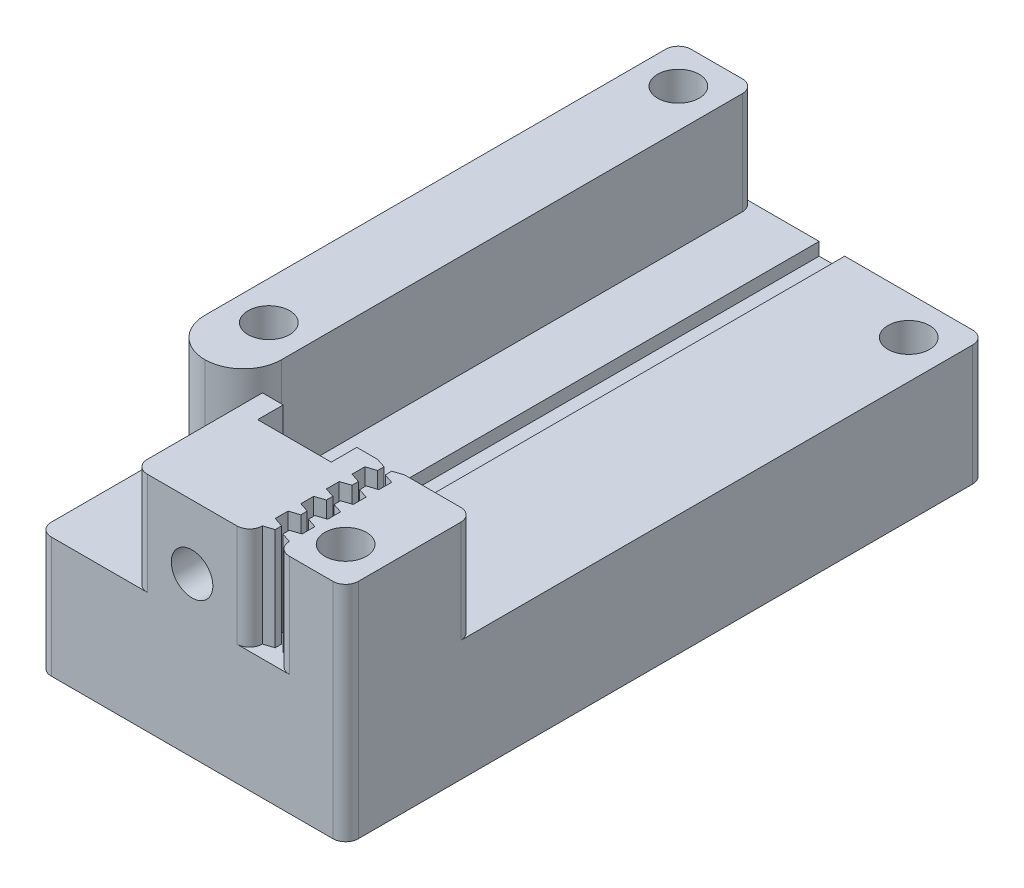
SolidWorks part; units mm, degrees
ref_plane "Front Plane" through (0, 0, 0) normal (0, 0, 1) x (1, 0, 0)
ref_plane "Top Plane" through (0, 0, 0) normal (0, 1, 0) x (1, 0, 0)
ref_plane "Right Plane" through (0, 0, 0) normal (1, 0, 0) x (0, 0, -1)
sketch "Sketch1" plane through (0, 0, 0) normal (0, 1, 0) x (1, 0, 0)
  line L0 (-12, 25) -> (12, -25) construction
  line L1 (-12, 25) -> (12, 25)
  line L2 (-12, 25) -> (-12, -25)
  line L3 (-12, -25) -> (12, -25)
  line L4 (12, 25) -> (12, -25)
  dimension "D1" = 24
  dimension "D2" = 50
extrude "Boss-Extrude1" add sketch "Sketch1" along normal blind 9.42
sketch "Sketch2" plane through (0, 9.42, 0) normal (0, 1, 0) x (1, 0, 0)
  line L0 (-12, -25) -> (12, -25) construction
  line L1 (-12, 25) -> (-6, 25)
  line L2 (-12, 25) -> (-12, -15)
  line L3 (-12, -15) -> (-6, -15)
  line L4 (-6, 25) -> (-6, -15)
  line L6 (-4.5, -25) -> (4.5, -25)
  line L7 (-4.5, -25) -> (-4.5, -15)
  line L8 (-4.5, -15) -> (4.5, -15)
  line L9 (4.5, -25) -> (4.5, -15)
  line L10 (12, -25) -> (6.6, -25)
  line L11 (12, -25) -> (12, -15)
  line L12 (12, -15) -> (6.6, -15)
  line L13 (6.6, -25) -> (6.6, -15)
  dimension "D1" = 6
  dimension "D2" = 10
  dimension "D3" = 1.5
  dimension "D4" = 2.1
  dimension "D5" = 9
  dimension "D6" = 10
extrude "Boss-Extrude2" add sketch "Sketch2" along normal blind 8
fillet "Fillet1" radius 3 2 edges at (-12, 13.42, 15) (-6, 13.42, 15)
sketch "Sketch4" plane through (0, 0, 15) normal (0, 0, -1) x (-1, 0, 0)
  line L0 (0, 17.42) -> (0, 12.42) construction
  line L1 (-4.5, 17.42) -> (4.5, 17.42) construction
  line L2 (-12, 0) -> (12, 0) construction
  circle A0 centre (0, 12.42) radius 1.625
  dimension "D1" = 3.25
  dimension "D2" = 12.42
extrude "Cut-Extrude2" cut sketch "Sketch4" against normal through all
sketch "Sketch5" plane through (0, 0, 15) normal (0, 0, -1) x (-1, 0, 0)
  line L0 (-2.875, 14.0799) -> (-2.875, 17.42)
  line L1 (0, 15.7398) -> (-2.875, 14.0799) construction
  line L2 (-2.875, 14.0799) -> (-2.875, 10.7601)
  line L3 (-2.875, 10.7601) -> (0, 9.1002)
  line L4 (0, 9.1002) -> (2.875, 10.7601)
  line L5 (2.875, 10.7601) -> (2.875, 14.0799)
  line L6 (2.875, 14.0799) -> (0, 15.7398) construction
  line L7 (-4.5, 17.42) -> (4.5, 17.42) construction
  line L8 (-2.875, 17.42) -> (2.875, 17.42)
  line L9 (2.875, 17.42) -> (2.875, 14.0799)
  line L10 (0, 12.42) -> (0, 17.42) construction
  circle A0 centre (0, 12.42) radius 2.875 construction
  dimension "D1" = 5.75
extrude "Cut-Extrude3" cut sketch "Sketch5" against normal blind 2
sketch "Sketch6" plane through (0, 9.42, 0) normal (0, 1, 0) x (1, 0, 0)
  line L0 (0, -15) -> (0, 25) construction
  line L2 (12, 25) -> (-6, 25) construction
  line L3 (2.875, -15) -> (0.5538, -15) construction
  line L4 (-1, 25) -> (1, 25)
  line L5 (-1, 25) -> (-1, -15)
  line L6 (-1, -15) -> (1, -15)
  line L7 (1, 25) -> (1, -15)
  dimension "D1" = 2
extrude "Cut-Extrude4" cut sketch "Sketch6" against normal blind 1
sketch "Sketch7" plane through (-12, 0, 0) normal (-1, 0, 0) x (0, 0, 1)
  line L0 (20, 0) -> (20, 4.93) construction
  line L1 (-25, 0) -> (25, 0) construction
  line L3 (25, 9.42) -> (25, 0) construction
  circle A0 centre (20, 4.93) radius 1.125
  dimension "D1" = 2.25
  dimension "D2" = 4.93
  dimension "D3" = 5
extrude "Cut-Extrude5" cut sketch "Sketch7" against normal blind 12
sketch "Sketch9" plane through (0, 0, 0) normal (0, -1, 0) x (1, 0, 0)
  line L4 (-12, 25) -> (-4.5, 25) construction
  line L8 (-9, 22) -> (-9, -22)
  line L9 (-9, -22) -> (9, -22)
  line L10 (9, -22) -> (9, 22)
  line L11 (9, 22) -> (-9, 22)
  line L12 (-9, 22) -> (-9, -22) construction
  line L13 (-9, -22) -> (9, -22) construction
  line L14 (9, -22) -> (9, 22) construction
  line L15 (9, 22) -> (-9, 22) construction
  circle A0 centre (9, 22) radius 1.625
  circle A1 centre (9, -22) radius 1.625
  circle A2 centre (-9, -22) radius 1.625
  circle A3 centre (-9, 10) radius 1.625
  point P11 (-8.25, 25)
  dimension "D2" = 3.25
  dimension "D3" = 15
  dimension "D1" = 3
extrude "Cut-Extrude6" cut sketch "Sketch9" against normal through all
fillet "Fillet2" radius 1 9 edges at (12, 4.71, -25) (12, 13.42, 15) (12, 8.71, 25) (4.5, 13.42, 25) (6.6, 13.42, 25) (-6, 13.42, -25) (-12, 8.71, -25) (-12, 4.71, 25) (-4.5, 13.42, 25)
sketch "Sketch10" plane through (0, 9.42, 0) normal (0, 1, 0) x (1, 0, 0)
  line L0 (4.5, -24) -> (6.6, -24) construction
  line L1 (5.55, -24) -> (5.55, 25) construction
  line L2 (11, 25) -> (1, 25) construction
  line L3 (4.5, -24) -> (4.5, -23)
  line L4 (4.5, -24) -> (4.5, -15) construction
  line L5 (4.5, -23) -> (5.25, -23.25)
  line L6 (5.25, -23.25) -> (5.25, -23.75)
  line L7 (5.25, -23.75) -> (4.5, -24)
  line L8 (4.5, -23.5) -> (5.25, -23.5) construction
  line L9 (6.6, -24) -> (6.6, -23)
  line L10 (5.85, -23.75) -> (6.6, -24)
  line L11 (5.85, -23.25) -> (5.85, -23.75)
  line L12 (6.6, -23) -> (5.85, -23.25)
  dimension "D1" = 0.75
  dimension "D2" = 1
  dimension "D3" = 0.5
extrude "Boss-Extrude3" add sketch "Sketch10" along normal up to surface (8 mm away) up to face at (0, 17.42, 19.2414)
pattern_linear "LPattern1" count 5 spacing 2 along (0, 0, -1) of "Boss-Extrude3"
